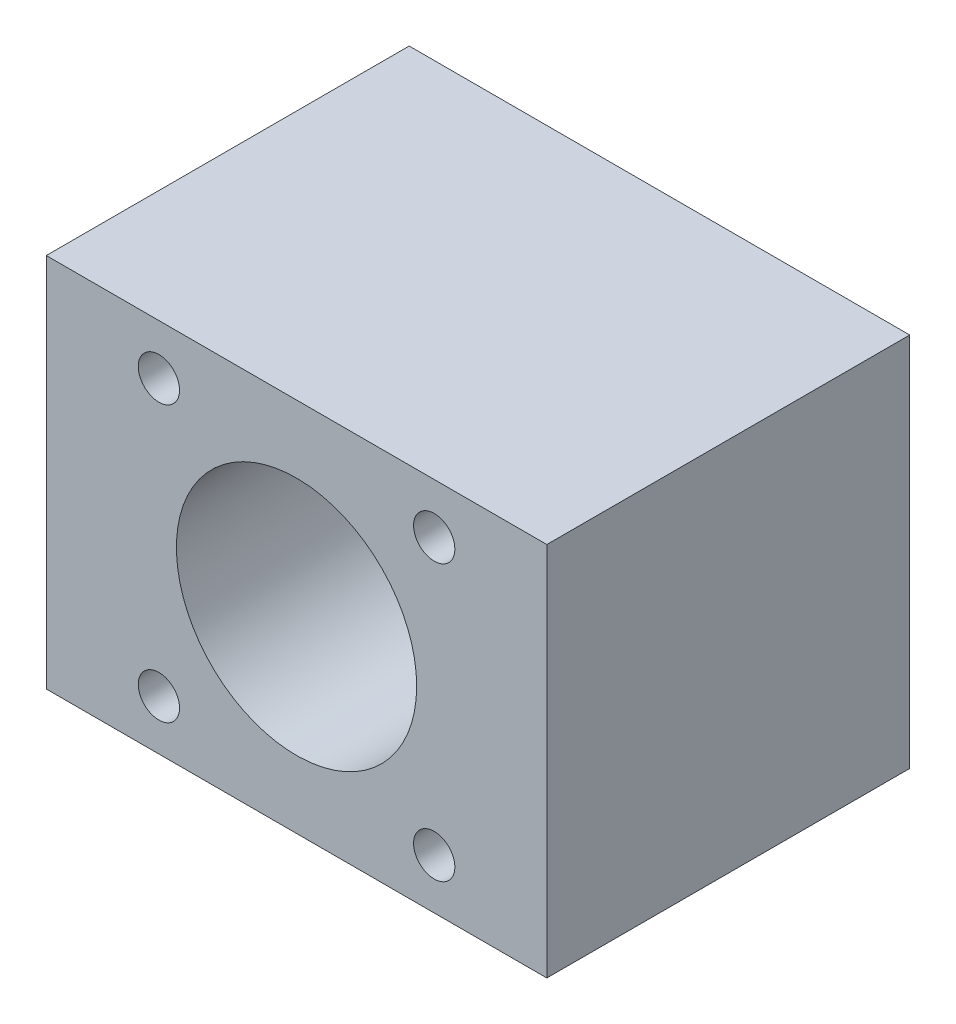
SolidWorks part; units mm, degrees
ref_plane "正面" through (0, 0, 0) normal (0, 0, 1) x (1, 0, 0)
ref_plane "平面" through (0, 0, 0) normal (0, 1, 0) x (1, 0, 0)
ref_plane "右側面" through (0, 0, 0) normal (1, 0, 0) x (0, 0, -1)
sketch "ｽｹｯﾁ1" plane through (0, 0, 0) normal (0, 0, 1) x (1, 0, 0)
  line L1 (-20, 15) -> (20, 15)
  line L2 (-20, 15) -> (-20, -15)
  line L3 (-20, -15) -> (20, -15)
  line L4 (20, 15) -> (20, -15)
  line L5 (-20, 15) -> (20, -15) construction
  line L6 (-20, -15) -> (20, 15) construction
  point P0 (0, 0)
  dimension "D1" = 40
  dimension "D2" = 30
extrude "ﾎﾞｽ - 押し出し1" add sketch "ｽｹｯﾁ1" along normal blind 29
sketch "ｽｹｯﾁ2" plane through (0, 0, 29) normal (0, 0, 1) x (1, 0, 0)
  line L0 (-20, 15) -> (-11, 15)
  line L1 (20, 15) -> (-20, 15) construction
  line L2 (-11, 15) -> (-11, 11)
  line L3 (20, 15) -> (11, 15)
  line L4 (11, 15) -> (11, 11)
  line L5 (-20, -15) -> (-11, -15)
  line L6 (-20, -15) -> (20, -15) construction
  line L7 (-11, -15) -> (-11, -11)
  line L8 (20, -15) -> (11, -15)
  line L9 (11, -15) -> (11, -11)
  circle A0 centre (0, 0) radius 9.6
  circle A1 centre (-11, 11) radius 1.6
  circle A2 centre (11, 11) radius 1.6
  circle A3 centre (-11, -11) radius 1.6
  circle A4 centre (11, -11) radius 1.6
  dimension "D1" = 19.2
  dimension "D10" = 3.2
  dimension "D11" = 3.2
  dimension "D12" = 3.2
  dimension "D13" = 3.2
  dimension "D2" = 9
  dimension "D3" = 9
  dimension "D4" = 9
  dimension "D5" = 9
  dimension "D6" = 4
  dimension "D7" = 4
  dimension "D8" = 4
  dimension "D9" = 4
extrude "ｶｯﾄ - 押し出し2" cut sketch "ｽｹｯﾁ2" against normal blind 29 contours A0 region at (0, 0, 29)
hole_wizard "M4x0.7 ねじ穴1" positions "ｽｹｯﾁ7" profile "ｽｹｯﾁ8" tap size "M4x0.7" standard "JIS"
sketch "ｽｹｯﾁ7" plane through (0, 0, 29) normal (0, 0, 1) x (1, 0, 0)
  point P0 (-11, 11)
  point P4 (11, 11)
  point P7 (11, -11)
  point P10 (-11, -11)
sketch "ｽｹｯﾁ8" plane through (-11, 11, 29) normal (1, 0, 0) x (0, -1, 0)
  line L0 (0, 0) -> (0, 15.4914)
  line L1 (0, 15.4914) -> (1.65, 14.5)
  line L2 (1.65, 14.5) -> (1.65, 0)
  line L5 (1.65, 0) -> (0, 0)
  line L10 (0, 15.4914) -> (-1.65, 14.5) construction
  line L11 (0, -6.35) -> (0, 107.95) construction
  dimension "ねじ下穴ﾄﾞﾘﾙ直径" = 3.3
  dimension "ねじ下穴ﾄﾞﾘﾙの深さ" = 14.5
  dimension "ﾄﾞﾘﾙ角度" = 118
cosmetic thread "穴のねじ山1" parameters "D1"=10, "D2"=4
cosmetic thread "穴のねじ山2" parameters "D1"=10, "D2"=4
cosmetic thread "穴のねじ山3" parameters "D1"=10, "D2"=4
cosmetic thread "穴のねじ山4" parameters "D1"=10, "D2"=4
cosmetic thread "穴のねじ山6" parameters "D1"=10, "D2"=4
cosmetic thread "穴のねじ山7" parameters "D1"=10, "D2"=4
hole_wizard "M4x0.7 ねじ穴2" positions "ｽｹｯﾁ10" profile "ｽｹｯﾁ11" tap size "M4x0.7" standard "JIS"
sketch "ｽｹｯﾁ10" plane through (0, 0, 0) normal (0, 0, -1) x (-1, 0, 0)
  point P0 (-11, 11)
  point P3 (11, 11)
  point P6 (11, -11)
  point P9 (-11, -11)
sketch "ｽｹｯﾁ11" plane through (11, 11, 0) normal (1, 0, 0) x (0, 1, 0)
  line L0 (0, 0) -> (0, 15.4914)
  line L1 (0, 15.4914) -> (1.65, 14.5)
  line L2 (1.65, 14.5) -> (1.65, 0)
  line L5 (1.65, 0) -> (0, 0)
  line L10 (0, 15.4914) -> (-1.65, 14.5) construction
  line L11 (0, -6.35) -> (0, 107.95) construction
  dimension "ねじ下穴ﾄﾞﾘﾙ直径" = 3.3
  dimension "ねじ下穴ﾄﾞﾘﾙの深さ" = 14.5
  dimension "ﾄﾞﾘﾙ角度" = 118
cosmetic thread "穴のねじ山5" parameters "D1"=10, "D2"=4
cosmetic thread "穴のねじ山8" parameters "D1"=10, "D2"=4
